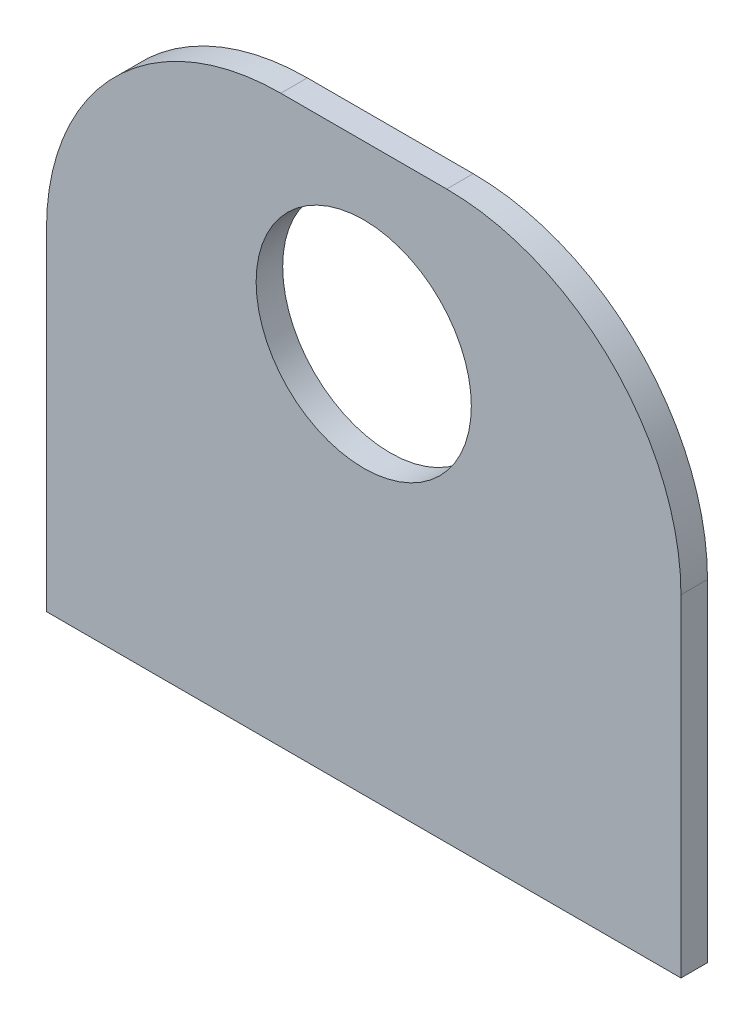
SolidWorks part; units mm, degrees
material "Beech"
ref_plane "Front Plane" through (0, 0, 0) normal (0, 0, 1) x (1, 0, 0)
ref_plane "Top Plane" through (0, 0, 0) normal (0, 1, 0) x (1, 0, 0)
ref_plane "Right Plane" through (0, 0, 0) normal (1, 0, 0) x (0, 0, -1)
sketch "Sketch1" plane through (0, 0, 0) normal (0, 0, 1) x (1, 0, 0)
  line L0 (-20.6375, 0) -> (20.6375, 0)
  line L46 (-20.6375, 0) -> (-20.6375, 36.83)
  line L47 (-20.6375, 36.83) -> (20.6375, 36.83)
  line L48 (20.6375, 0) -> (20.6375, 36.83)
  line L49 (-20.6375, 25.4) -> (20.6375, 25.4) construction
  circle A0 centre (0, 25.4) radius 7
  point P1 (0, 0)
  point P56 (0, 25.4)
  dimension "D14" = 11.43
  dimension "D3" = 14
  dimension "D2" = 36.83
  dimension "D12" = 41.275
extrude "Boss-Extrude1" add sketch "Sketch1" along normal blind 1.7272 contours L49 L46 L0 L48 A0 | L46 L49 A0 L48 L47 region at (0, 11.9291, 0) region at (-20.2092, 31.115, 0)
fillet "Fillet7" radius 15.24 2 edges at (-20.6375, 36.83, 0.8636) (20.6375, 36.83, 0.8636)
